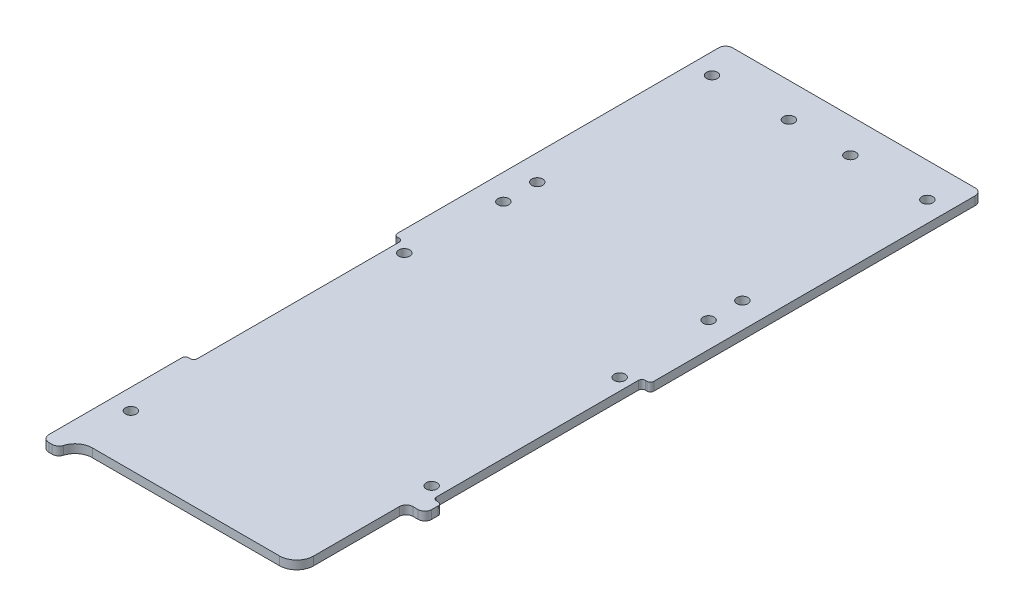
SolidWorks part; units mm, degrees
ref_plane "Front Plane" through (0, 0, 0) normal (0, 0, 1) x (1, 0, 0)
ref_plane "Top Plane" through (0, 0, 0) normal (0, 1, 0) x (1, 0, 0)
ref_plane "Right Plane" through (0, 0, 0) normal (1, 0, 0) x (0, 0, -1)
sketch "Sketch1" plane through (0, 0, 0) normal (0, 1, 0) x (1, 0, 0)
  line L0 (-39.9997, 0) -> (-39.9997, 114.3) construction
  line L1 (-47.625, 127) -> (47.625, 127)
  line L2 (-47.625, 127) -> (-47.625, -127)
  line L3 (-47.625, -127) -> (47.625, -127)
  line L4 (47.625, 127) -> (47.625, -127)
  line L5 (-47.625, 127) -> (47.625, -127) construction
  line L6 (-47.625, -127) -> (47.625, 127) construction
  line L7 (0, 0) -> (0, 127) construction
  line L8 (-39.9997, 0) -> (-39.9997, -101.6) construction
  line L9 (-39.9997, 0) -> (0, 0) construction
  line L10 (-41.275, -127) -> (-41.275, -120.65)
  line L11 (-41.275, -120.65) -> (41.275, -120.65)
  line L12 (41.275, -120.65) -> (41.275, -127)
  line L13 (-39.9997, 114.3) -> (-11.4247, 114.3) construction
  line L14 (39.9997, 114.3) -> (11.4247, 114.3) construction
  circle A0 centre (-39.9997, 114.3) radius 2.032
  circle A1 centre (-39.9997, 0) radius 2.032
  circle A2 centre (-39.9997, -101.6) radius 2.032
  circle A3 centre (39.9997, -101.6) radius 2.032
  circle A4 centre (39.9997, 0) radius 2.032
  circle A5 centre (39.9997, 114.3) radius 2.032
  circle A6 centre (-11.4247, 114.3) radius 2.032
  circle A7 centre (11.4247, 114.3) radius 2.032
  circle A8 centre (-39.9997, -69.85) radius 2.032
  circle A9 centre (39.9997, -69.85) radius 2.032
  point P0 (0, 0)
  dimension "D4" = 4.064
  dimension "D10" = 28.575
  dimension "D1" = 95.25
  dimension "D2" = 254
  dimension "D3" = 7.6253
  dimension "D5" = 12.7
  dimension "D6" = 25.4
  dimension "D7" = 6.35
  dimension "D8" = 6.35
  dimension "D9" = 6.35
  dimension "D11" = 69.85
extrude "Boss-Extrude1" add sketch "Sketch1" along normal blind 3.175 contours L4 L1 L2 L3 A4 A0 A1 A2 A3 A5 | A8 | A3 region at (0, 0, -2.6944) region at (39.9997, 0, 101.6) region at (-39.9997, 0, 69.85)
fillet "Fillet1" radius 2.54 4 edges at (-47.625, 1.5875, -127) (47.625, 1.5875, -127) (47.625, 1.5875, 127) (-47.625, 1.5875, 127)
fillet "Fillet2" radius 2.54 2 edges at (41.275, 1.5875, 127) (-41.275, 1.5875, 127)
fillet "Fillet3" radius 6.35 2 edges at (41.275, 1.5875, 120.65) (-41.275, 1.5875, 120.65)
sketch "Sketch2" plane through (0, 0, 0) normal (0, -1, 0) x (1, 0, 0)
  line L0 (41.9123, 131.8831) -> (41.9123, 109.8659) construction
  line L1 (41.9123, 109.8659) -> (41.9123, 106.3879) construction
  line L2 (41.9123, 83.271) -> (41.9123, 82.5325) construction
  line L3 (41.9123, 82.5325) -> (41.9123, 81.2514) construction
  line L4 (41.9123, 83.271) -> (41.9123, 106.3879) construction
  line L5 (41.9123, 131.8831) -> (41.9123, 109.8659)
  line L6 (41.9123, 109.8659) -> (41.9123, 106.3879)
  line L7 (41.9123, 83.271) -> (41.9123, 82.5325)
  line L8 (41.9123, 82.5325) -> (41.9123, 81.2514)
  line L9 (41.9123, 83.271) -> (41.9123, 106.3879)
  line L10 (41.9123, 81.2514) -> (47.625, 81.2514)
  line L11 (47.625, -124.46) -> (47.625, 124.46) construction
  line L12 (41.9123, 131.8831) -> (47.625, 131.8831)
  line L13 (47.625, 131.8831) -> (47.625, 81.2514)
  line L14 (40.6423, 79.9814) -> (48.895, 79.9814)
  line L15 (48.895, 133.1531) -> (48.895, 79.9814)
  line L16 (40.6423, 133.1531) -> (48.895, 133.1531)
  line L17 (40.6423, 133.1531) -> (40.6423, 109.8659)
  line L18 (40.6423, 109.8659) -> (40.6423, 106.3879)
  line L19 (40.6423, 83.271) -> (40.6423, 106.3879)
  line L20 (40.6423, 83.271) -> (40.6423, 82.5325)
  line L21 (40.6423, 82.5325) -> (40.6423, 79.9814)
  arc M7 (43.815, 127) -> (41.3809, 125.1857) centre (43.815, 124.46) ccw
  arc M8 (41.3809, 125.1857) -> (35.2956, 120.65) centre (35.2956, 127) cw
  line M18 (47.625, -124.46) -> (47.625, 124.46)
  dimension "D1" = 1.27
extrude "Cut-Extrude1" cut sketch "Sketch2" against normal through all contours L20 L21 L14 L10 L8 L7 L9 L19 M18 | L19 L9 L6 L5 L17 L18 M7 M8 | L13 L10 L8 L7 L9 L6 L5 L12 region at (41.6772, 0, 99.9819)
fillet "Fillet4" radius 6.35 1 edges at (40.6423, 1.5875, 123.5743)
fillet "Fillet5" radius 2.54 2 edges at (47.625, 1.5875, 79.9814) (40.6423, 1.5875, 79.9814)
sketch "Sketch3" plane through (0, 0, 0) normal (0, -1, 0) x (1, 0, 0)
  line L0 (-36.3083, -49.7791) -> (-39.9151, -49.7791) construction
  line L1 (-40.4231, -49.276) -> (-40.4231, -45.7043) construction
  line L2 (-35.8003, -45.7043) -> (-35.8003, -49.276) construction
  line L3 (-39.9151, -45.2013) -> (-36.3083, -45.2013) construction
  line L4 (-36.3083, -37.2027) -> (-39.9151, -37.2027) construction
  line L5 (-35.8003, -33.1279) -> (-35.8003, -36.6996) construction
  line L6 (-40.4231, -36.6996) -> (-40.4231, -33.1279) construction
  line L7 (-39.9151, -32.6249) -> (-36.3083, -32.6249) construction
  line L8 (36.2849, -32.6249) -> (39.8917, -32.6249) construction
  line L9 (40.3997, -33.1279) -> (40.3997, -36.6996) construction
  line L10 (39.8917, -37.2027) -> (36.2849, -37.2027) construction
  line L11 (35.7769, -36.6996) -> (35.7769, -33.1279) construction
  line L12 (36.2849, -45.2013) -> (39.8917, -45.2013) construction
  line L13 (35.7769, -49.276) -> (35.7769, -45.7043) construction
  line L14 (40.3997, -45.7043) -> (40.3997, -49.276) construction
  line L15 (39.8917, -49.7791) -> (36.2849, -49.7791) construction
  line L16 (-36.3083, -49.7791) -> (-39.9151, -49.7791)
  line L17 (-40.4231, -49.276) -> (-40.4231, -45.7043)
  line L18 (-35.8003, -45.7043) -> (-35.8003, -49.276)
  line L19 (-39.9151, -45.2013) -> (-36.3083, -45.2013)
  line L20 (-36.3083, -37.2027) -> (-39.9151, -37.2027)
  line L21 (-35.8003, -33.1279) -> (-35.8003, -36.6996)
  line L22 (-40.4231, -36.6996) -> (-40.4231, -33.1279)
  line L23 (-39.9151, -32.6249) -> (-36.3083, -32.6249)
  line L24 (36.2849, -32.6249) -> (39.8917, -32.6249)
  line L25 (40.3997, -33.1279) -> (40.3997, -36.6996)
  line L26 (39.8917, -37.2027) -> (36.2849, -37.2027)
  line L27 (35.7769, -36.6996) -> (35.7769, -33.1279)
  line L28 (36.2849, -45.2013) -> (39.8917, -45.2013)
  line L29 (35.7769, -49.276) -> (35.7769, -45.7043)
  line L30 (40.3997, -45.7043) -> (40.3997, -49.276)
  line L31 (39.8917, -49.7791) -> (36.2849, -49.7791)
  line L32 (-47.625, -25.836) -> (47.625, -25.836)
  line L33 (-47.625, -124.46) -> (-47.625, 124.46) construction
  line L34 (47.625, -124.46) -> (47.625, 77.4414) construction
  line L35 (0, -25.836) -> (0, -56.0686) construction
  line L38 (134.3625, -51.414) -> (184.1383, -51.414)
  line L39 (184.1383, -51.414) -> (184.1383, -43.4909)
  line L40 (184.1383, -43.4909) -> (182.3349, -43.4909)
  line L41 (181.8269, -42.9878) -> (181.8269, -39.4161)
  line L42 (182.3349, -38.9131) -> (184.1383, -38.9131)
  line L43 (184.1383, -38.9131) -> (184.1383, -30.9899)
  line L44 (184.1383, -30.9899) -> (134.3625, -30.9899)
  line L45 (134.3625, -30.9899) -> (133.3383, -32.0042)
  line L46 (133.3383, -32.0042) -> (132.3141, -30.9899)
  line L47 (132.3141, -30.9899) -> (70.8625, -30.9899)
  line L48 (70.8625, -30.9899) -> (69.8383, -32.0042)
  line L49 (69.8383, -32.0042) -> (68.8141, -30.9899)
  line L50 (68.8141, -30.9899) -> (7.3625, -30.9899)
  line L51 (7.3625, -30.9899) -> (6.3383, -32.0042)
  line L52 (6.3383, -32.0042) -> (5.3141, -30.9899)
  line L53 (5.3141, -30.9899) -> (-56.1375, -30.9899)
  line L54 (-56.1375, -30.9899) -> (-57.1617, -32.0042)
  line L55 (-57.1617, -32.0042) -> (-58.1859, -30.9899)
  line L56 (-58.1859, -30.9899) -> (-119.6375, -30.9899)
  line L57 (-119.6375, -30.9899) -> (-120.6617, -32.0042)
  line L58 (-120.6617, -32.0042) -> (-121.6859, -30.9899)
  line L59 (-121.6859, -30.9899) -> (-184.1617, -30.9899)
  line L60 (-184.1617, -30.9899) -> (-184.1617, -51.414)
  line L61 (-184.1617, -51.414) -> (-121.6859, -51.414)
  line L62 (-121.6859, -51.414) -> (-120.6617, -50.3998)
  line L63 (-120.6617, -50.3998) -> (-119.6375, -51.414)
  line L64 (-119.6375, -51.414) -> (-58.1859, -51.414)
  line L65 (-58.1859, -51.414) -> (-57.1617, -50.3998)
  line L66 (-57.1617, -50.3998) -> (-56.1375, -51.414)
  line L67 (-56.1375, -51.414) -> (5.3141, -51.414)
  line L68 (5.3141, -51.414) -> (6.3383, -50.3998)
  line L69 (6.3383, -50.3998) -> (7.3625, -51.414)
  line L70 (7.3625, -51.414) -> (68.8141, -51.414)
  line L71 (68.8141, -51.414) -> (69.8383, -50.3998)
  line L72 (69.8383, -50.3998) -> (70.8625, -51.414)
  line L73 (70.8625, -51.414) -> (132.3141, -51.414)
  line L74 (132.3141, -51.414) -> (133.3383, -50.3998)
  line L75 (133.3383, -50.3998) -> (134.3625, -51.414)
  line L76 (134.3625, -51.414) -> (184.1383, -51.414)
  line L77 (184.1383, -51.414) -> (184.1383, -43.4909)
  line L78 (184.1383, -43.4909) -> (182.3349, -43.4909)
  line L79 (181.8269, -42.9878) -> (181.8269, -39.4161)
  line L80 (182.3349, -38.9131) -> (184.1383, -38.9131)
  line L81 (184.1383, -38.9131) -> (184.1383, -30.9899)
  line L82 (184.1383, -30.9899) -> (134.3625, -30.9899)
  line L83 (134.3625, -30.9899) -> (133.3383, -32.0042)
  line L84 (133.3383, -32.0042) -> (132.3141, -30.9899)
  line L85 (132.3141, -30.9899) -> (70.8625, -30.9899)
  line L86 (70.8625, -30.9899) -> (69.8383, -32.0042)
  line L87 (69.8383, -32.0042) -> (68.8141, -30.9899)
  line L88 (68.8141, -30.9899) -> (7.3625, -30.9899)
  line L89 (7.3625, -30.9899) -> (6.3383, -32.0042)
  line L90 (6.3383, -32.0042) -> (5.3141, -30.9899)
  line L91 (5.3141, -30.9899) -> (-56.1375, -30.9899)
  line L92 (-56.1375, -30.9899) -> (-57.1617, -32.0042)
  line L93 (-57.1617, -32.0042) -> (-58.1859, -30.9899)
  line L94 (-58.1859, -30.9899) -> (-119.6375, -30.9899)
  line L95 (-119.6375, -30.9899) -> (-120.6617, -32.0042)
  line L96 (-120.6617, -32.0042) -> (-121.6859, -30.9899)
  line L97 (-121.6859, -30.9899) -> (-184.1617, -30.9899)
  line L98 (-184.1617, -30.9899) -> (-184.1617, -51.414)
  line L99 (-184.1617, -51.414) -> (-121.6859, -51.414)
  line L100 (-121.6859, -51.414) -> (-120.6617, -50.3998)
  line L101 (-120.6617, -50.3998) -> (-119.6375, -51.414)
  line L102 (-119.6375, -51.414) -> (-58.1859, -51.414)
  line L103 (-58.1859, -51.414) -> (-57.1617, -50.3998)
  line L104 (-57.1617, -50.3998) -> (-56.1375, -51.414)
  line L105 (-56.1375, -51.414) -> (5.3141, -51.414)
  line L106 (5.3141, -51.414) -> (6.3383, -50.3998)
  line L107 (6.3383, -50.3998) -> (7.3625, -51.414)
  line L108 (7.3625, -51.414) -> (68.8141, -51.414)
  line L109 (68.8141, -51.414) -> (69.8383, -50.3998)
  line L110 (69.8383, -50.3998) -> (70.8625, -51.414)
  line L111 (70.8625, -51.414) -> (132.3141, -51.414)
  line L112 (132.3141, -51.414) -> (133.3383, -50.3998)
  line L113 (133.3383, -50.3998) -> (134.3625, -51.414)
  line L1362 (-40.4231, -34.9138) -> (-35.8003, -34.9138)
  line L1857 (-38.1117, -32.6249) -> (-38.1117, -37.2027)
  line L1858 (-38.1117, -45.2013) -> (-38.1117, -49.7791)
  line L1859 (-40.4231, -47.4902) -> (-35.8003, -47.4902)
  circle A0 centre (-38.1117, -34.9138) radius 2.032
  circle A1 centre (-38.1117, -47.4902) radius 2.032
  circle A2 centre (38.1117, -47.4902) radius 2.032
  circle A3 centre (38.1117, -34.9138) radius 2.032
  ellipse E0 centre (-39.9151, -45.7043) end of major axis (-39.4071, -45.7043) minor radius 0.5031 (-39.9151, -45.2013) -> (-40.4231, -45.7043) ccw construction
  ellipse E1 centre (-39.9151, -49.276) end of major axis (-39.4071, -49.276) minor radius 0.5031 (-40.4231, -49.276) -> (-39.9151, -49.7791) ccw construction
  ellipse E2 centre (182.3349, -42.9878) end of major axis (182.8429, -42.9878) minor radius 0.5031 (181.8269, -42.9878) -> (182.3349, -43.4909) ccw
  ellipse E3 centre (182.3349, -39.4161) end of major axis (182.8429, -39.4161) minor radius 0.5031 (182.3349, -38.9131) -> (181.8269, -39.4161) ccw
  ellipse E4 centre (182.3349, -42.9878) end of major axis (182.8429, -42.9878) minor radius 0.5031 (181.8269, -42.9878) -> (182.3349, -43.4909) ccw
  ellipse E5 centre (182.3349, -39.4161) end of major axis (182.8429, -39.4161) minor radius 0.5031 (182.3349, -38.9131) -> (181.8269, -39.4161) ccw
  ellipse E6 centre (-36.3083, -49.276) end of major axis (-35.8003, -49.276) minor radius 0.5031 (-36.3083, -49.7791) -> (-35.8003, -49.276) ccw construction
  ellipse E7 centre (-36.3083, -45.7043) end of major axis (-35.8003, -45.7043) minor radius 0.5031 (-35.8003, -45.7043) -> (-36.3083, -45.2013) ccw construction
  ellipse E8 centre (-39.9151, -36.6996) end of major axis (-39.4071, -36.6996) minor radius 0.5031 (-40.4231, -36.6996) -> (-39.9151, -37.2027) ccw construction
  ellipse E9 centre (-36.3083, -36.6996) end of major axis (-35.8003, -36.6996) minor radius 0.5031 (-36.3083, -37.2027) -> (-35.8003, -36.6996) ccw construction
  ellipse E10 centre (-36.3083, -33.1279) end of major axis (-35.8003, -33.1279) minor radius 0.5031 (-35.8003, -33.1279) -> (-36.3083, -32.6249) ccw construction
  ellipse E11 centre (-39.9151, -33.1279) end of major axis (-39.4071, -33.1279) minor radius 0.5031 (-39.9151, -32.6249) -> (-40.4231, -33.1279) ccw construction
  ellipse E12 centre (39.8917, -33.1279) end of major axis (40.3997, -33.1279) minor radius 0.5031 (40.3997, -33.1279) -> (39.8917, -32.6249) ccw construction
  ellipse E13 centre (36.2849, -33.1279) end of major axis (36.7929, -33.1279) minor radius 0.5031 (36.2849, -32.6249) -> (35.7769, -33.1279) ccw construction
  ellipse E14 centre (39.8917, -36.6996) end of major axis (40.3997, -36.6996) minor radius 0.5031 (39.8917, -37.2027) -> (40.3997, -36.6996) ccw construction
  ellipse E15 centre (36.2849, -36.6996) end of major axis (36.7929, -36.6996) minor radius 0.5031 (35.7769, -36.6996) -> (36.2849, -37.2027) ccw construction
  ellipse E16 centre (36.2849, -45.7043) end of major axis (36.7929, -45.7043) minor radius 0.5031 (36.2849, -45.2013) -> (35.7769, -45.7043) ccw construction
  ellipse E17 centre (36.2849, -49.276) end of major axis (36.7929, -49.276) minor radius 0.5031 (35.7769, -49.276) -> (36.2849, -49.7791) ccw construction
  ellipse E18 centre (39.8917, -45.7043) end of major axis (40.3997, -45.7043) minor radius 0.5031 (40.3997, -45.7043) -> (39.8917, -45.2013) ccw construction
  ellipse E19 centre (39.8917, -49.276) end of major axis (40.3997, -49.276) minor radius 0.5031 (39.8917, -49.7791) -> (40.3997, -49.276) ccw construction
  ellipse E20 centre (-39.9151, -45.7043) end of major axis (-39.4071, -45.7043) minor radius 0.5031 (-39.9151, -45.2013) -> (-40.4231, -45.7043) ccw
  ellipse E21 centre (-39.9151, -49.276) end of major axis (-39.4071, -49.276) minor radius 0.5031 (-40.4231, -49.276) -> (-39.9151, -49.7791) ccw
  ellipse E22 centre (-36.3083, -49.276) end of major axis (-35.8003, -49.276) minor radius 0.5031 (-36.3083, -49.7791) -> (-35.8003, -49.276) ccw
  ellipse E23 centre (-36.3083, -45.7043) end of major axis (-35.8003, -45.7043) minor radius 0.5031 (-35.8003, -45.7043) -> (-36.3083, -45.2013) ccw
  ellipse E24 centre (-39.9151, -36.6996) end of major axis (-39.4071, -36.6996) minor radius 0.5031 (-40.4231, -36.6996) -> (-39.9151, -37.2027) ccw
  ellipse E25 centre (-36.3083, -36.6996) end of major axis (-35.8003, -36.6996) minor radius 0.5031 (-36.3083, -37.2027) -> (-35.8003, -36.6996) ccw
  ellipse E26 centre (-36.3083, -33.1279) end of major axis (-35.8003, -33.1279) minor radius 0.5031 (-35.8003, -33.1279) -> (-36.3083, -32.6249) ccw
  ellipse E27 centre (-39.9151, -33.1279) end of major axis (-39.4071, -33.1279) minor radius 0.5031 (-39.9151, -32.6249) -> (-40.4231, -33.1279) ccw
  ellipse E28 centre (39.8917, -33.1279) end of major axis (40.3997, -33.1279) minor radius 0.5031 (40.3997, -33.1279) -> (39.8917, -32.6249) ccw
  ellipse E29 centre (36.2849, -33.1279) end of major axis (36.7929, -33.1279) minor radius 0.5031 (36.2849, -32.6249) -> (35.7769, -33.1279) ccw
  ellipse E30 centre (39.8917, -36.6996) end of major axis (40.3997, -36.6996) minor radius 0.5031 (39.8917, -37.2027) -> (40.3997, -36.6996) ccw
  ellipse E31 centre (36.2849, -36.6996) end of major axis (36.7929, -36.6996) minor radius 0.5031 (35.7769, -36.6996) -> (36.2849, -37.2027) ccw
  ellipse E32 centre (36.2849, -45.7043) end of major axis (36.7929, -45.7043) minor radius 0.5031 (36.2849, -45.2013) -> (35.7769, -45.7043) ccw
  ellipse E33 centre (36.2849, -49.276) end of major axis (36.7929, -49.276) minor radius 0.5031 (35.7769, -49.276) -> (36.2849, -49.7791) ccw
  ellipse E34 centre (39.8917, -45.7043) end of major axis (40.3997, -45.7043) minor radius 0.5031 (40.3997, -45.7043) -> (39.8917, -45.2013) ccw
  ellipse E35 centre (39.8917, -49.276) end of major axis (40.3997, -49.276) minor radius 0.5031 (39.8917, -49.7791) -> (40.3997, -49.276) ccw
  dimension "D2" = 4.064
  dimension "D1" = 0
extrude "Cut-Extrude2" cut sketch "Sketch3" against normal through all contours A0 | A1 | A2 | A3
sketch "Sketch4" plane through (0, 3.175, 0) normal (0, 1, 0) x (1, 0, 0)
  line L0 (-44.45, 3.81) -> (-46.99, 3.81) construction
  line L1 (-46.99, 3.81) -> (-46.99, 121.92) construction
  line L2 (-42.545, 126.365) -> (-0.635, 126.365) construction
  line L3 (-0.635, 126.365) -> (-0.635, 107.95) construction
  line L4 (-6.35, 102.235) -> (-15.875, 102.235) construction
  line L5 (-22.86, 95.25) -> (-22.86, -115.57) construction
  line L6 (-27.305, -120.015) -> (-35.4551, -120.015) construction
  line L7 (-43.815, -126.365) -> (-45.085, -126.365) construction
  line L8 (-46.99, -124.46) -> (-46.99, -73.7819) construction
  line L9 (-46.99, -73.7819) -> (-44.45, -73.7819) construction
  line L10 (-44.45, -73.7819) -> (-44.45, 3.81) construction
  line L11 (-46.99, 3.81) -> (-44.45, 3.81)
  line L12 (-46.99, 121.92) -> (-46.99, 3.81)
  line L13 (-0.635, 126.365) -> (-42.545, 126.365)
  line L14 (-0.635, 107.95) -> (-0.635, 126.365)
  line L15 (-15.875, 102.235) -> (-6.35, 102.235)
  line L16 (-22.86, -115.57) -> (-22.86, 95.25)
  line L17 (-35.4551, -120.015) -> (-27.305, -120.015)
  line L18 (-45.085, -126.365) -> (-43.815, -126.365)
  line L19 (-46.99, -73.7819) -> (-46.99, -124.46)
  line L20 (-44.45, -73.7819) -> (-46.99, -73.7819)
  line L21 (-44.45, 3.81) -> (-44.45, -73.7819)
  line L22 (-46.99, 3.81) -> (-44.45, 3.81)
  line L23 (-46.99, 121.92) -> (-46.99, 3.81)
  line L24 (-0.635, 126.365) -> (-42.545, 126.365)
  line L25 (-0.635, 107.95) -> (-0.635, 126.365)
  line L26 (-15.875, 102.235) -> (-6.35, 102.235)
  line L27 (-22.86, -115.57) -> (-22.86, 95.25)
  line L28 (-35.4551, -120.015) -> (-27.305, -120.015)
  line L29 (-45.085, -126.365) -> (-43.815, -126.365)
  line L30 (-46.99, -73.7819) -> (-46.99, -124.46)
  line L31 (-44.45, -73.7819) -> (-46.99, -73.7819)
  line L32 (-44.45, 3.81) -> (-44.45, -73.7819)
  line L33 (40.64, -77.5286) -> (40.64, -117.0408) construction
  line L34 (35.4551, -120.015) -> (27.305, -120.015) construction
  line L35 (22.86, -115.57) -> (22.86, 95.25) construction
  line L36 (15.875, 102.235) -> (6.35, 102.235) construction
  line L37 (0.635, 107.95) -> (0.635, 126.365) construction
  line L38 (0.635, 126.365) -> (42.545, 126.365) construction
  line L39 (46.99, 121.92) -> (46.99, 3.81) construction
  line L40 (46.99, 3.81) -> (44.45, 3.81) construction
  line L41 (44.45, 3.81) -> (44.45, -73.7819) construction
  line L42 (44.45, -73.7819) -> (46.99, -73.7819) construction
  line L43 (46.99, -73.7819) -> (46.99, -77.5286) construction
  line L44 (46.99, -77.5286) -> (40.64, -77.5286) construction
  line L45 (-44.45, 3.81) -> (-46.99, 3.81)
  line L46 (-46.99, 3.81) -> (-46.99, 121.92)
  line L47 (-42.545, 126.365) -> (-0.635, 126.365)
  line L48 (-0.635, 126.365) -> (-0.635, 107.95)
  line L49 (-6.35, 102.235) -> (-15.875, 102.235)
  line L50 (-22.86, 95.25) -> (-22.86, -115.57)
  line L51 (-27.305, -120.015) -> (-35.4551, -120.015)
  line L52 (-43.815, -126.365) -> (-45.085, -126.365)
  line L53 (-46.99, -124.46) -> (-46.99, -73.7819)
  line L54 (-46.99, -73.7819) -> (-44.45, -73.7819)
  line L55 (-44.45, -73.7819) -> (-44.45, 3.81)
  line L56 (40.64, -77.5286) -> (40.64, -117.0408)
  line L57 (35.4551, -120.015) -> (27.305, -120.015)
  line L58 (22.86, -115.57) -> (22.86, 95.25)
  line L59 (15.875, 102.235) -> (6.35, 102.235)
  line L60 (0.635, 107.95) -> (0.635, 126.365)
  line L61 (0.635, 126.365) -> (42.545, 126.365)
  line L62 (46.99, 121.92) -> (46.99, 3.81)
  line L63 (46.99, 3.81) -> (44.45, 3.81)
  line L64 (44.45, 3.81) -> (44.45, -73.7819)
  line L65 (44.45, -73.7819) -> (46.99, -73.7819)
  line L66 (46.99, -73.7819) -> (46.99, -77.5286)
  line L67 (46.99, -77.5286) -> (40.64, -77.5286)
  line L178 (-46.99, 3.81) -> (-47.625, 3.81)
  line L179 (-47.625, 124.46) -> (-47.625, -124.46) construction
  line L180 (-46.99, -73.7819) -> (-47.625, -73.7819)
  line L181 (46.99, -73.7819) -> (47.625, -73.7819)
  line L182 (47.625, 124.46) -> (47.625, -77.4414) construction
  line L183 (46.99, 3.81) -> (47.625, 3.81)
  arc A0 (-42.545, 126.365) -> (-46.99, 121.92) centre (-42.545, 121.92) ccw construction
  arc A1 (-6.35, 102.235) -> (-0.635, 107.95) centre (-6.35, 107.95) ccw construction
  arc A2 (-15.875, 102.235) -> (-22.86, 95.25) centre (-15.875, 95.25) ccw construction
  arc A3 (-27.305, -120.015) -> (-22.86, -115.57) centre (-27.305, -115.57) ccw construction
  arc A4 (-35.4551, -120.015) -> (-41.9138, -124.3399) centre (-35.4551, -127) ccw construction
  arc A5 (-43.815, -126.365) -> (-41.9138, -124.3399) centre (-43.815, -124.46) ccw construction
  arc A6 (-46.99, -124.46) -> (-45.085, -126.365) centre (-45.085, -124.46) ccw construction
  arc A7 (-42.545, 126.365) -> (-46.99, 121.92) centre (-42.545, 121.92) ccw
  arc A8 (-6.35, 102.235) -> (-0.635, 107.95) centre (-6.35, 107.95) ccw
  arc A9 (-15.875, 102.235) -> (-22.86, 95.25) centre (-15.875, 95.25) ccw
  arc A10 (-27.305, -120.015) -> (-22.86, -115.57) centre (-27.305, -115.57) ccw
  arc A11 (-35.4551, -120.015) -> (-41.9138, -124.3399) centre (-35.4551, -127) ccw
  arc A12 (-43.815, -126.365) -> (-41.9138, -124.3399) centre (-43.815, -124.46) ccw
  arc A13 (-46.99, -124.46) -> (-45.085, -126.365) centre (-45.085, -124.46) ccw
  arc A14 (-42.545, 126.365) -> (-46.99, 121.92) centre (-42.545, 121.92) ccw
  arc A15 (-6.35, 102.235) -> (-0.635, 107.95) centre (-6.35, 107.95) ccw
  arc A16 (-15.875, 102.235) -> (-22.86, 95.25) centre (-15.875, 95.25) ccw
  arc A17 (-27.305, -120.015) -> (-22.86, -115.57) centre (-27.305, -115.57) ccw
  arc A18 (-35.4551, -120.015) -> (-41.9138, -124.3399) centre (-35.4551, -127) ccw
  arc A19 (-43.815, -126.365) -> (-41.9138, -124.3399) centre (-43.815, -124.46) ccw
  arc A20 (-46.99, -124.46) -> (-45.085, -126.365) centre (-45.085, -124.46) ccw
  arc A21 (36.8369, -120.153) -> (40.64, -117.0408) centre (37.465, -117.0408) ccw construction
  arc A22 (36.8369, -120.153) -> (35.4551, -120.015) centre (35.4551, -127) ccw construction
  arc A23 (22.86, -115.57) -> (27.305, -120.015) centre (27.305, -115.57) ccw construction
  arc A24 (22.86, 95.25) -> (15.875, 102.235) centre (15.875, 95.25) ccw construction
  arc A25 (0.635, 107.95) -> (6.35, 102.235) centre (6.35, 107.95) ccw construction
  arc A26 (46.99, 121.92) -> (42.545, 126.365) centre (42.545, 121.92) ccw construction
  arc A27 (-42.545, 126.365) -> (-46.99, 121.92) centre (-42.545, 121.92) ccw
  arc A28 (-6.35, 102.235) -> (-0.635, 107.95) centre (-6.35, 107.95) ccw
  arc A29 (-15.875, 102.235) -> (-22.86, 95.25) centre (-15.875, 95.25) ccw
  arc A30 (-27.305, -120.015) -> (-22.86, -115.57) centre (-27.305, -115.57) ccw
  arc A31 (-35.4551, -120.015) -> (-41.9138, -124.3399) centre (-35.4551, -127) ccw
  arc A32 (-43.815, -126.365) -> (-41.9138, -124.3399) centre (-43.815, -124.46) ccw
  arc A33 (-46.99, -124.46) -> (-45.085, -126.365) centre (-45.085, -124.46) ccw
  arc A34 (36.8369, -120.153) -> (40.64, -117.0408) centre (37.465, -117.0408) ccw
  arc A35 (36.8369, -120.153) -> (35.4551, -120.015) centre (35.4551, -127) ccw
  arc A36 (22.86, -115.57) -> (27.305, -120.015) centre (27.305, -115.57) ccw
  arc A37 (22.86, 95.25) -> (15.875, 102.235) centre (15.875, 95.25) ccw
  arc A38 (0.635, 107.95) -> (6.35, 102.235) centre (6.35, 107.95) ccw
  arc A39 (46.99, 121.92) -> (42.545, 126.365) centre (42.545, 121.92) ccw
  line M32 (47.625, -77.4414) -> (47.625, 124.46)
  line M36 (-47.625, 124.46) -> (-47.625, -124.46)
  dimension "D1" = 0
extrude "Cut-Extrude3" cut sketch "Sketch4" against normal through all and the other way through all contours L180 L31 L32 L22 L178 M36 | L183 L63 L64 L65 L181 M32 region at (-46.0375, 3.175, 34.9859) region at (46.0375, 3.175, 34.9859)
fillet "Fillet6" radius 1.27 8 edges at (-44.45, 1.5875, -3.81) (-44.45, 1.5875, 73.7819) (44.45, 1.5875, -3.81) (44.45, 1.5875, 73.7819) (47.625, 1.5875, 73.7819) (47.625, 1.5875, -3.81) (-47.625, 1.5875, 73.7819) (-47.625, 1.5875, -3.81)
